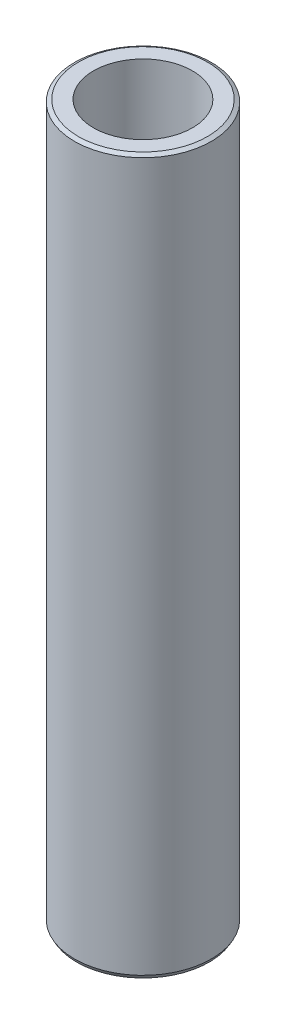
SolidWorks part; units mm, degrees
ref_plane "Front Plane" through (0, 0, 0) normal (0, 0, 1) x (1, 0, 0)
ref_plane "Top Plane" through (0, 0, 0) normal (0, 1, 0) x (1, 0, 0)
ref_plane "Right Plane" through (0, 0, 0) normal (1, 0, 0) x (0, 0, -1)
sketch "Sketch1" plane through (0, 0, 0) normal (0, 1, 0) x (1, 0, 0)
  circle A0 centre (0, 0) radius 57.5
  dimension "SHAFT_OD" = 115
extrude "Boss-Extrude1" add sketch "Sketch1" along normal blind 600
sketch "Sketch2" plane through (0, 0, 0) normal (0, 1, 0) x (1, 0, 0)
  circle A0 centre (0, 0) radius 41.554
  dimension "BORE_D" = 83.1081
extrude "Cut-Extrude1" cut sketch "Sketch2" along normal through all
chamfer "Chamfer1" distance 1.8584 angle 60.415 2 edges at (0, 600, 57.5) (0, 0, 57.5) first distance on face at (0, 600, 57.5) first distance on face at (0, 0, 41.554)
